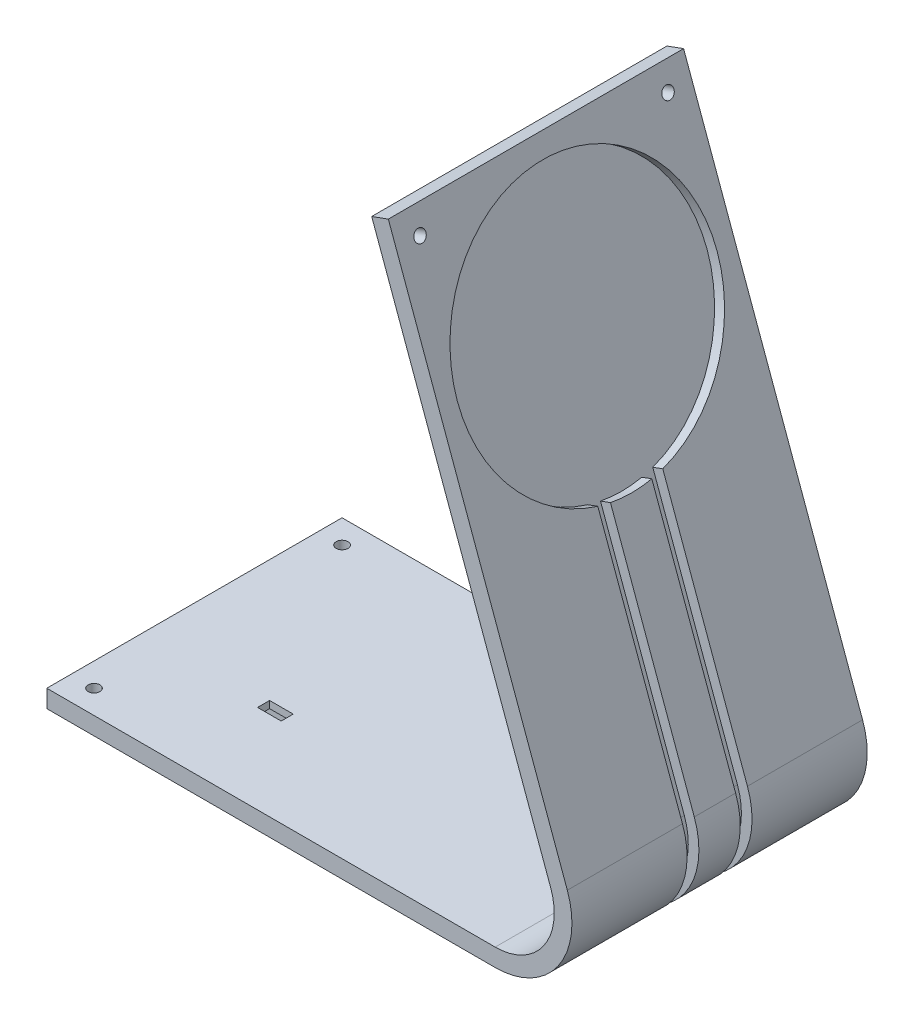
SolidWorks part; units mm, degrees
ref_plane "前视基准面" through (0, 0, 0) normal (0, 0, 1) x (1, 0, 0)
ref_plane "上视基准面" through (0, 0, 0) normal (0, 1, 0) x (1, 0, 0)
ref_plane "右视基准面" through (0, 0, 0) normal (1, 0, 0) x (0, 0, -1)
other "Configuration Table"
sketch "草图2" plane through (0, 0, 0) normal (0, 0, 1) x (1, 0, 0)
  line L0 (-42.6188, 0) -> (33.3109, 0)
  line L5 (42.7078, 13.4202) -> (12.3985, 96.6944)
  line L6 (42.7078, 13.4202) -> (9.2861, 105.2456) construction
  line L7 (-42.6188, -5) -> (-42.6188, 0) construction
  line L8 (33.3109, 0) -> (33.3109, -1) construction
  line L10 (15.2773, 97.8486) -> (12.3643, 96.7883) construction
  line L11 (-42.6188, 0) -> (33.3109, 0) construction
  arc A0 (33.3109, 0) -> (42.7078, 13.4202) centre (33.3109, 10) ccw
  dimension "D2" = 10
  dimension "D1" = 0.1
extrude "整体拉伸-薄壁1" add sketch "草图2" along normal mid plane 50 thin thin type one direction wall 3
sketch "草图4" plane through (44.8442, 16.3219, 0) normal (0.9397, 0.342, 0) x (0, 0, -1)
  line L0 (-25, 86.6225) -> (25, 86.6225) construction
  circle A0 centre (0, 61.2225) radius 22
  dimension "D1" = 44
  dimension "D2" = 25.4
extrude "中间圆切除-拉伸1" cut sketch "草图4" against normal blind 1.8
sketch "草图3" plane through (0, 0, 0) normal (0, 0, 1) x (1, 0, 0)
  line L0 (45.5269, 14.4463) -> (15.2176, 97.7204) construction
  line L1 (45.5269, 14.4463) -> (15.2176, 97.7204) construction
  line L2 (-42.6188, -3) -> (33.3109, -3) construction
  line L3 (-42.6188, -3) -> (33.3109, -3) construction
  line L4 (8.763, -1.2) -> (33.3109, -1.2)
  line L5 (43.8354, 13.8306) -> (29.7379, 52.5634)
  line L6 (43.8354, 13.8306) -> (13.5261, 97.1048) construction
  line L7 (-42.6188, -1.2) -> (33.3109, -1.2) construction
  line L9 (29.7379, 52.5634) -> (31.4293, 53.179) construction
  line L16 (29.7379, 52.5634) -> (28.7118, 55.3824)
  arc A0 (33.3109, 0) -> (42.7078, 13.4202) centre (33.3109, 10) ccw construction
  arc A1 (33.3109, -3) -> (45.5269, 14.4463) centre (33.3109, 10) ccw construction
  arc A2 (33.3109, -1.2) -> (43.8354, 13.8306) centre (33.3109, 10) ccw
  dimension "D2" = 3
  dimension "D1" = 1.8
extrude "线槽切除-拉伸-薄壁1" cut sketch "草图3" against normal blind 2 from offset 5.5 thin thin type one direction wall 1.8
mirror "镜向1" about plane through (0, 0, 0) normal (0, 0, 1) of "线槽切除-拉伸-薄壁1"
sketch "草图5" plane through (44.8442, 16.3219, 0) normal (0.9397, 0.342, 0) x (0, 0, -1)
  line L0 (-25, -1.9961) -> (-25, 86.6225) construction
  line L1 (-25, 86.6225) -> (25, 86.6225) construction
  circle A0 centre (-21, 82.6225) radius 1
  dimension "D1" = 2
  dimension "D3" = 4
  dimension "D2" = 4
extrude "螺丝孔切除-拉伸2" cut sketch "草图5" against normal up to next
mirror "镜向2" about plane through (0, 0, 0) normal (0, 0, 1) of "螺丝孔切除-拉伸2"
sketch "草图6" plane through (0, 0, 0) normal (0, 1, 0) x (1, 0, 0)
  line L0 (-42.6188, -25) -> (33.3109, -25) construction
  line L1 (-42.6188, -25) -> (-42.6188, 25) construction
  circle A0 centre (-38.6188, -21) radius 1
  dimension "D1" = 2
  dimension "D2" = 4
  dimension "D3" = 4
extrude "下螺丝孔切除-拉伸3" cut sketch "草图6" against normal up to next
mirror "镜向3" about plane through (0, 0, 0) normal (0, 0, 1) of "下螺丝孔切除-拉伸3"
sketch "草图7" plane through (0, -3, 0) normal (0, -1, 0) x (1, 0, 0)
  line L1 (-40.9188, -5.9) -> (-26.9188, -5.9)
  line L2 (-42.6188, -4.6) -> (-42.6188, 4.6)
  line L3 (-40.9188, 5.9) -> (-26.9188, 5.9)
  line L4 (-26.9188, -5.9) -> (-26.9188, 5.9)
  line L7 (-42.6188, -4.6) -> (-40.9188, -4.6)
  line L9 (-42.6188, 4.6) -> (-40.9188, 4.6)
  line L11 (-40.9188, 4.6) -> (-40.9188, 5.9)
  line L12 (-40.9188, -4.6) -> (-40.9188, -5.9)
  line L14 (-34.1188, -4.5) -> (-41.6188, -4.5) construction
  line L15 (-42.6188, 25) -> (-42.6188, -25) construction
  line L18 (-27.0188, 5.8) -> (-40.8188, 5.8) construction
  line L19 (-40.8188, -5.8) -> (-27.0188, -5.8) construction
  line L20 (-27.0188, -5.8) -> (-27.0188, 5.8) construction
  line L21 (-40.8188, 5.8) -> (-40.8188, 4.5) construction
  dimension "D1" = 0.1
  dimension "D2" = 9.2
  dimension "D3" = 0.1
  dimension "D4" = 0.1
  dimension "D5" = 0.1
  dimension "D6" = 0.1
extrude "切除-拉伸1" cut sketch "草图7" against normal blind 1.8
sketch "草图8" plane through (0, -1.2, 0) normal (0, -1, 0) x (1, 0, 0)
  line L1 (-42.6188, -4.6) -> (-40.9188, -4.6)
  line L2 (-42.6188, -4.6) -> (-42.6188, 4.6)
  line L3 (-42.6188, 4.6) -> (-40.9188, 4.6)
  line L4 (-40.9188, -4.6) -> (-40.9188, 4.6)
extrude "凸台-拉伸1" add sketch "草图8" along normal blind 1.7
sketch "草图12" plane through (0, -3, 0) normal (0, -1, 0) x (1, 0, 0)
  line L1 (-10.1, -8.1) -> (-10.1, -10.6)
  line L2 (-10.1, -10.6) -> (15.1, -10.6)
  line L3 (15.1, -10.6) -> (15.1, 10.6)
  line L4 (15.1, 10.6) -> (-10.1, 10.6)
  line L5 (-13.1, 8.1) -> (-13.1, -8.1)
  line L7 (-13.1, -8.1) -> (-10.1, -8.1)
  line L8 (-13.1, 8.1) -> (-10.1, 8.1)
  line L9 (-10.1, 8.1) -> (-10.1, 10.6)
  line L10 (-10, 8) -> (-13, 8) construction
  line L11 (-10, 10.5) -> (-10, 8) construction
  line L12 (7, 10.5) -> (-10, 10.5) construction
  line L13 (15, -3.5) -> (15, 3.5) construction
  line L14 (-10, -10.5) -> (7, -10.5) construction
  line L15 (-10, -8) -> (-10, -10.5) construction
  line L16 (-13, -8) -> (-10, -8) construction
  line L17 (-13, 8) -> (-13, -8) construction
  dimension "D1" = 0.1
  dimension "D2" = 0.1
  dimension "D3" = 0.1
  dimension "D4" = 0.1
  dimension "D5" = 0.1
  dimension "D6" = 0.1
  dimension "D7" = 0.1
  dimension "D8" = 0.1
extrude "零件切除-拉伸2" cut sketch "草图12" against normal blind 2
sketch "草图14" plane through (0, -3, 0) normal (0, -1, 0) x (1, 0, 0)
  line L0 (-13.1, 8.1) -> (-13.1, -8.1) construction
  line L1 (-26.9188, -8.1) -> (-13.1, -8.1)
  line L2 (-26.9188, -8.1) -> (-26.9188, 10.8)
  line L3 (-26.9188, 10.8) -> (-13.1, 10.8)
  line L4 (-13.1, -8.1) -> (-13.1, 10.8)
  line L5 (-24.2094, 10.7) -> (-15.7094, 10.7) construction
  line L6 (-13.1, -8.1) -> (-10.1, -8.1) construction
  line L8 (-26.9188, -5.9) -> (-26.9188, 5.9) construction
  dimension "D1" = 0.1
extrude "切除-拉伸3" cut sketch "草图14" against normal blind 1.8
sketch "草图15" plane through (0, -1.2, 0) normal (0, -1, 0) x (1, 0, 0)
  line L0 (-13.1, 10.8) -> (-26.9188, 10.8) construction
  line L1 (-25.3094, 6.1) -> (-14.6094, 6.1)
  line L2 (-25.3094, 6.1) -> (-25.3094, 10.8)
  line L3 (-25.3094, 10.8) -> (-24.3094, 10.8)
  line L4 (-14.6094, 6.1) -> (-14.6094, 10.8)
  line L5 (-24.3094, 7.1) -> (-15.6094, 7.1)
  line L6 (-24.3094, 7.1) -> (-24.3094, 10.8)
  line L8 (-15.6094, 7.1) -> (-15.6094, 10.8)
  line L9 (-15.6094, 10.8) -> (-14.6094, 10.8)
  line L10 (-24.2094, 7.2) -> (-24.2094, 10.7) construction
  line L11 (-15.7094, 10.7) -> (-15.7094, 7.2) construction
  line L12 (-15.7094, 7.2) -> (-24.2094, 7.2) construction
  point P15 (-14.6094, 8.45)
  dimension "D1" = 0.1
  dimension "D2" = 0.1
  dimension "D3" = 1
  dimension "D4" = 1
  dimension "D5" = 1
  dimension "D6" = 0.1
extrude "凸台-拉伸2" add sketch "草图15" along normal up to surface (1.8 mm away) up to face at (-38.6188, -3, 22)
sketch "草图16" plane through (0, 0, 0) normal (0, 1, 0) x (1, 0, 0)
  line L0 (-18.1594, -9.77) -> (-18.1594, -8.13) construction
  line L1 (-17.9594, -7.93) -> (-21.9594, -7.93)
  line L2 (-17.9594, -7.93) -> (-17.9594, -9.97)
  line L3 (-17.9594, -9.97) -> (-21.9594, -9.97)
  line L4 (-21.9594, -7.93) -> (-21.9594, -9.97)
  line L5 (-21.7594, -9.77) -> (-19.9594, -9.77) construction
  line L6 (-18.1594, -8.13) -> (-19.9594, -8.13) construction
  line L7 (-21.7594, -8.13) -> (-21.7594, -9.77) construction
  dimension "D1" = 0.2
  dimension "D2" = 0.2
  dimension "D3" = 0.2
  dimension "D4" = 0.2
extrude "切除-拉伸4" cut sketch "草图16" against normal up to surface (1.2 mm away) up to face at (-23.7424, -1.2, 3.6385)
